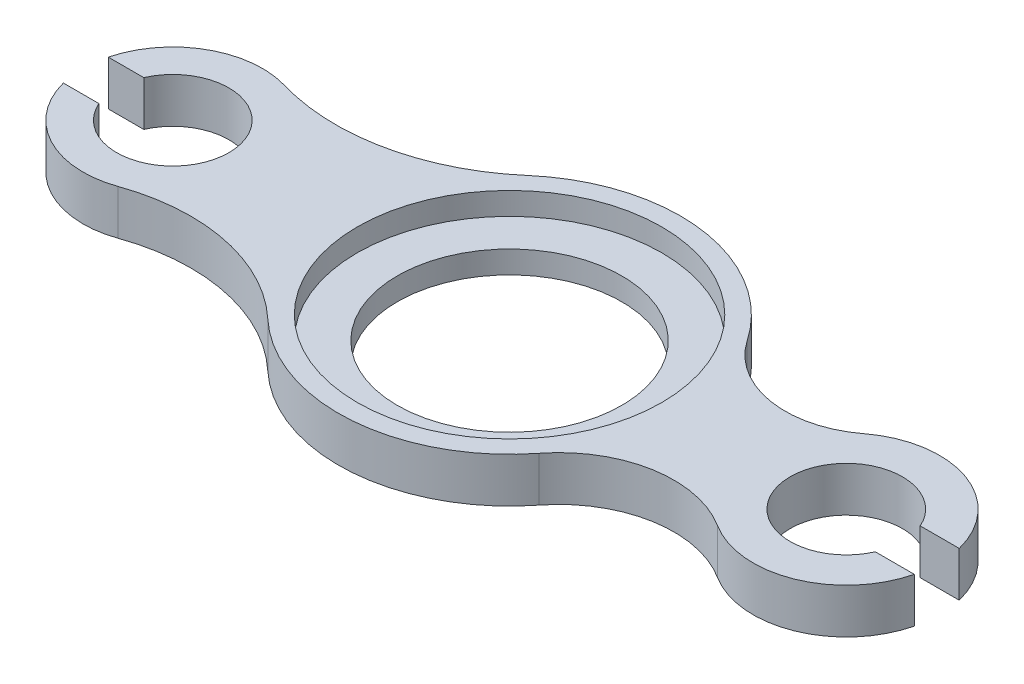
SolidWorks part; units mm, degrees
ref_plane "Front Plane" through (0, 0, 0) normal (0, 0, 1) x (1, 0, 0)
ref_plane "Top Plane" through (0, 0, 0) normal (0, 1, 0) x (1, 0, 0)
ref_plane "Right Plane" through (0, 0, 0) normal (1, 0, 0) x (0, 0, -1)
sketch "Sketch1" plane through (0, 0, 0) normal (0, 1, 0) x (1, 0, 0)
  line L0 (-192.0901, 0) -> (306.7735, 0) construction
  line L1 (-80.1583, 113.3523) -> (-80.1583, -124.7159) construction
  line L2 (219.8417, 113.3523) -> (219.8417, -131.5341) construction
  line L3 (69.8417, 113.3523) -> (69.8417, -124.7159) construction
  line L5 (-118.8881, 10) -> (-103.0712, 10)
  line L7 (-118.8881, -10) -> (-103.0712, -10)
  line L9 (242.7546, 10) -> (260.1475, 10)
  line L11 (242.7546, -10) -> (260.1475, -10)
  circle A0 centre (69.8417, 0) radius 50
  circle A1 centre (69.8417, 0) radius 67.8
  arc A2 (-103.0712, -10) -> (-103.0712, 10) centre (-80.1583, 0) ccw
  arc A3 (242.7546, 10) -> (242.7546, -10) centre (219.8417, 0) ccw
  arc A4 (17.6404, -55.4762) -> (129.8878, -46.8727) centre (69.8417, 0) ccw
  arc A5 (-68.9546, 38.3989) -> (-118.8881, 10) centre (-80.1583, 0) ccw
  arc A6 (197.6461, -35.0985) -> (260.1475, -10) centre (219.8417, 0) ccw
  arc A7 (-68.9546, 38.3989) -> (20.1305, 57.7182) centre (-42.2017, 130.0902) ccw
  arc A8 (17.6404, -55.4762) -> (-66.8102, -37.7071) centre (-39.1539, -115.8335) ccw
  arc A9 (197.6461, -35.0985) -> (129.8878, -46.8727) centre (170.2672, -78.3934) ccw
  arc A10 (132.7335, 42.9792) -> (194.644, 33.0096) centre (168.4185, 67.3657) ccw
  arc A11 (132.7335, 42.9792) -> (20.1305, 57.7182) centre (69.8417, 0) ccw
  arc A12 (-118.8881, -10) -> (-66.8102, -37.7071) centre (-80.1583, 0) ccw
  arc A13 (260.1475, 10) -> (194.644, 33.0096) centre (219.8417, 0) ccw
  dimension "D3" = 50
  dimension "D4" = 50
  dimension "D5" = 100
  dimension "D6" = 135.6
  dimension "D1" = 150
  dimension "D2" = 150
extrude "Boss-Extrude1" add sketch "Sketch1" along normal blind 20 contours L9 A13 A10 A11 A7 A5 L5 A2 L7 A12 A8 A4 A9 A6 L11 A3 A1 region at (-97.9136, 0, -31.2191)
extrude "Boss-Extrude2" add sketch "Sketch1<3>" along normal blind 10 contours A1 A0 region at (3.9594, 0, 0)
sketch "Sketch1<3>" plane through (0, 0, 0) normal (0, 1, 0) x (1, 0, 0) same geometry as "Sketch1"
